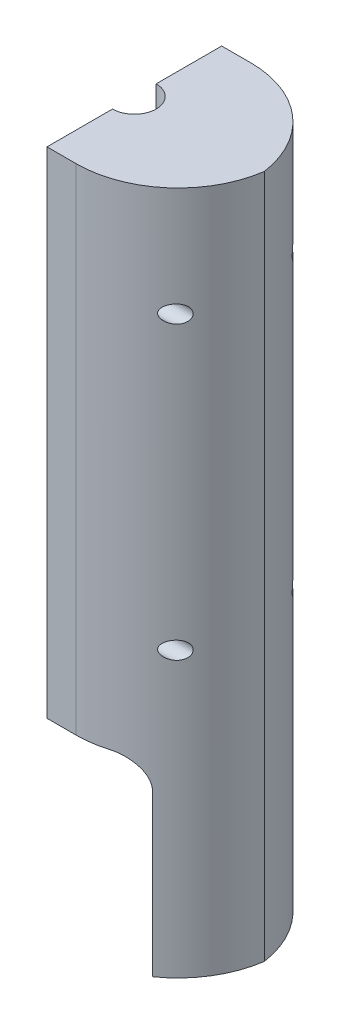
SolidWorks part; units mm, degrees
ref_plane "Plan de face" through (0, 0, 0) normal (0, 0, 1) x (1, 0, 0)
ref_plane "Plan de dessus" through (0, 0, 0) normal (0, 1, 0) x (1, 0, 0)
ref_plane "Plan de droite" through (0, 0, 0) normal (1, 0, 0) x (0, 0, -1)
sketch "Esquisse1" plane through (0, 0, 0) normal (0, 0, 1) x (1, 0, 0)
  line L0 (-139.3911, 131.107) -> (-139.3911, -98.893)
  line L1 (-139.3911, -98.893) -> (-124.3911, -98.893)
  line L2 (-124.3911, -98.893) -> (-124.3911, -33.893)
  line L3 (-124.3911, -33.893) -> (-64.3911, -33.893)
  line L4 (-64.3911, -33.893) -> (-64.3911, -98.893)
  line L5 (-64.3911, -98.893) -> (-49.3911, -98.893)
  line L6 (-49.3911, -98.893) -> (-49.3911, 131.107)
  line L7 (-49.3911, 131.107) -> (-139.3911, 131.107)
  dimension "D1" = 230
  dimension "D2" = 90
  dimension "D3" = 60
  dimension "D4" = 15
extrude "Boss.-Extru.1" add sketch "Esquisse1" along normal blind 60
fillet "Congé4" radius 35 1 edges at (-139.3911, 16.107, 60)
fillet "Congé5" radius 35 1 edges at (-139.3911, 16.107, 0)
fillet "Congé6" radius 35 2 edges at (-49.3911, 16.107, 0) (-49.3911, 16.107, 60)
fillet "Congé12" radius 10 2 edges at (-124.3911, -33.893, 29.5186) (-64.3911, -33.893, 30)
sketch "Esquisse5" plane through (0, 131.107, 0) normal (0, 1, 0) x (1, 0, 0)
  line L0 (-94.3911, -60) -> (-94.3911, 0)
  line L1 (-84.3911, -60) -> (-104.3911, -60) construction
  arc A0 (-94.3911, -60) -> (-94.3911, 0) centre (-123.4668, -30) cw
extrude "Enlèv. mat.-Extru.8" cut sketch "Esquisse5" against normal blind 251
sketch "Esquisse6" plane through (-94.3911, 0, 0) normal (-1, 0, 0) x (0, 0, 1)
  line L0 (30, 131.107) -> (30, -33.893) construction
  line L1 (60, 131.107) -> (0, 131.107) construction
  line L2 (60, -33.893) -> (0, -33.893) construction
  line L4 (60, -33.893) -> (60, 131.107) construction
  line L5 (60, 48.607) -> (0, 48.607) construction
  line L6 (0, -33.893) -> (0, 131.107) construction
  circle A0 centre (10, 98.607) radius 2
  circle A1 centre (50, 98.607) radius 2
  circle A2 centre (50, -1.393) radius 2
  circle A3 centre (10, -1.393) radius 2
  dimension "D1" = 40
  dimension "D2" = 50
extrude "Enlèv. mat.-Extru.9" cut sketch "Esquisse6" against normal blind 58
sketch "Esquisse9" plane through (0, 131.107, 0) normal (0, 1, 0) x (1, 0, 0)
  line L0 (-94.3911, -60) -> (-94.3911, 0) construction
  line L1 (-49.7501, -30) -> (-94.3911, -30) construction
  arc A0 (-94.3911, -22.5) -> (-94.3911, -37.5) centre (-94.3911, -30) cw
  point P8 (-86.8911, -30)
  dimension "D1" = 15
extrude "Enlèv. mat.-Extru.12" cut sketch "Esquisse9" against normal blind 179 and the other way through all flip side to cut
shell "Coque1" thickness 5 removed face at (-82.4875, 131.107, 30)
ref_plane "Plan2" through (-49.7501, 0, 0) normal (-1, 0, 0) x (0, 0, 1)
sketch "Esquisse11" plane through (-49.7501, 0, 0) normal (-1, 0, 0) x (0, 0, 1)
  circle A0 centre (50, -1.393) radius 2 construction
  circle A1 centre (50, 98.607) radius 2 construction
  circle A2 centre (50, -1.393) radius 2
  circle A3 centre (50, 98.607) radius 2
  circle A4 centre (10, 98.607) radius 2 construction
  circle A5 centre (10, -1.393) radius 2 construction
  circle A6 centre (10, 98.607) radius 2
  circle A7 centre (10, -1.393) radius 2
  circle A8 centre (50, 98.607) radius 3
  circle A9 centre (10, 98.607) radius 3
  circle A10 centre (50, -1.393) radius 3
  circle A11 centre (10, -1.393) radius 3
extrude "Enlèv. mat.-Extru.14" cut sketch "Esquisse11" along normal blind 20
sketch "Esquisse12" plane through (0, 131.107, 0) normal (0, 1, 0) x (1, 0, 0)
  line L0 (-84.3911, 0) -> (-94.3911, 0) construction
  line L1 (-94.3911, -22.5) -> (-94.3911, 0) construction
  line L2 (-94.3911, -60) -> (-94.3911, -37.5) construction
  line L3 (-84.3911, -60) -> (-94.3911, -60) construction
  line L4 (-84.3911, 0) -> (-94.3911, 0)
  line L5 (-94.3911, -22.5) -> (-94.3911, 0)
  line L6 (-94.3911, -60) -> (-94.3911, -37.5)
  line L7 (-84.3911, -60) -> (-94.3911, -60)
  arc A0 (-94.3911, -37.5) -> (-94.3911, -22.5) centre (-94.3911, -30) ccw construction
  arc A1 (-84.3911, -60) -> (-49.7501, -30) centre (-84.3911, -25) ccw construction
  arc A2 (-49.7501, -30) -> (-84.3911, 0) centre (-84.3911, -35) ccw construction
  arc A3 (-94.3911, -37.5) -> (-94.3911, -22.5) centre (-94.3911, -30) ccw
  arc A4 (-84.3911, -60) -> (-49.7501, -30) centre (-84.3911, -25) ccw
  arc A5 (-49.7501, -30) -> (-84.3911, 0) centre (-84.3911, -35) ccw
extrude "Boss.-Extru.2" add sketch "Esquisse12" along normal blind 5
sketch "Esquisse13" plane through (-64.3911, 0, 0) normal (-1, 0, 0) x (0, 0, 1)
  line L0 (30, -43.893) -> (30, -98.893) construction
  line L1 (53.7228, -43.893) -> (6.2772, -43.893) construction
  line L2 (53.7228, -98.893) -> (6.2772, -98.893) construction
  line L4 (53.7228, -98.893) -> (53.7228, -43.893) construction
  line L5 (53.7228, -71.393) -> (6.2772, -71.393) construction
  line L6 (6.2772, -43.893) -> (6.2772, -98.893) construction
  line L7 (26, -56.393) -> (34, -56.393)
  line L8 (26, -56.393) -> (26, -86.393)
  line L9 (26, -86.393) -> (34, -86.393)
  line L10 (34, -56.393) -> (34, -86.393)
  line L11 (26, -56.393) -> (34, -86.393) construction
  line L12 (26, -86.393) -> (34, -56.393) construction
  line L13 (15, -67.393) -> (45, -67.393)
  line L14 (15, -67.393) -> (15, -75.393)
  line L15 (15, -75.393) -> (45, -75.393)
  line L16 (45, -67.393) -> (45, -75.393)
  line L17 (15, -67.393) -> (45, -75.393) construction
  line L18 (15, -75.393) -> (45, -67.393) construction
  point P12 (30, -71.393)
  point P17 (30, -71.393)
extrude "Enlèv. mat.-Extru.15" cut sketch "Esquisse13" against normal blind 4 contours L8 L13 L10 L7 | L8 L15 L10 L13 | L14 L15 L8 L13 | L16 L13 L10 L15 | L15 L8 L9 L10 region at (-64.3911, -61.893, 30) region at (-64.3911, -71.393, 30) region at (-64.3911, -71.393, 20.5) region at (-64.3911, -71.393, 39.5) region at (-64.3911, -80.893, 30)
